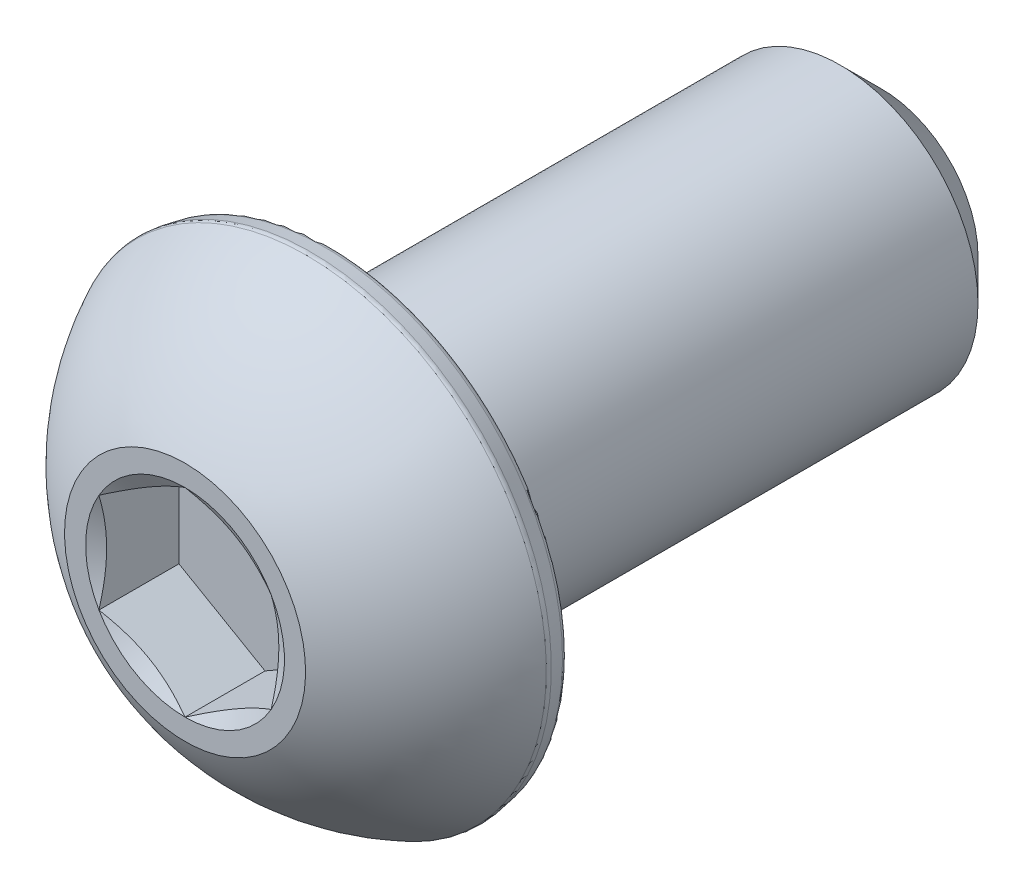
SolidWorks part; units mm, degrees
material "Plain Carbon Steel"
ref_plane "Front Plane" through (0, 0, 0) normal (0, 0, 1) x (1, 0, 0)
ref_plane "Top Plane" through (0, 0, 0) normal (0, 1, 0) x (1, 0, 0)
ref_plane "Right Plane" through (0, 0, 0) normal (1, 0, 0) x (0, 0, -1)
sketch "Sketch1" plane through (0, 0, 0) normal (1, 0, 0) x (0, 0, -1)
  line L0 (-8.0264, 0) -> (8.0264, 0) construction
  line L1 (-8.0264, 0) -> (-8.0264, 5.5499)
  line L2 (-8.0264, 5.5499) -> (-4.6736, 5.5499)
  line L3 (-4.6736, 5.5499) -> (-4.6736, 3.175)
  line L4 (-4.6736, 3.175) -> (8.0264, 3.175)
  line L5 (8.0264, 3.175) -> (8.0264, 0)
  point P2 (0, 0)
  point P4 (6.7564, 0)
  point P9 (6.1214, 3.175)
  point P10 (6.1214, -3.175)
  point P11 (8.0264, -3.175)
  point P15 (-6.1824, 0)
  dimension "Head Height" = 3.3528
  dimension "Head Diameter" = 11.0998
  dimension "Length" = 12.7
  dimension "Screw Size Decimal Equivalent" = 6.35
  dimension "Thread Pitch" = 1.27
  dimension "D1" = 1.905
  dimension "D2" = 1.844
sketch "Sketch2" plane through (0, 0, 0) normal (0, 0, 1) x (1, 0, 0)
  line L0 (0, 3.175) -> (0, 0) construction
  line L1 (0, 2.2914) -> (-1.9844, 1.1457)
  line L2 (-1.9844, 1.1457) -> (-1.9844, -1.1457)
  line L3 (-1.9844, -1.1457) -> (0, -2.2914)
  line L4 (0, -2.2914) -> (1.9844, -1.1457)
  line L5 (1.9844, -1.1457) -> (1.9844, 1.1457)
  line L6 (1.9844, 1.1457) -> (0, 2.2914)
  circle A0 centre (0, 0) radius 1.9844 construction
  circle A1 centre (0, 0) radius 2.7781
  point P10 (0, 2.7781)
  dimension "D1" = 5.5563
  dimension "Drive Size" = 3.9688
sketch "Sketch3" plane through (0, 0, 0) normal (1, 0, 0) x (0, 0, -1)
  line L0 (-8.0264, 0) -> (-8.0264, 2.7781)
  line L1 (-8.0264, 0) -> (-8.0264, 5.5499) construction
  line L2 (-8.0264, 5.5499) -> (-4.6736, 5.5499) construction
  line L3 (-5.1765, 5.5499) -> (-4.6736, 5.4612)
  line L4 (-4.6736, 5.5499) -> (-4.6736, 3.175) construction
  line L5 (-4.6736, 5.4612) -> (-4.6736, 3.175)
  line L6 (-8.0264, 0) -> (8.0264, 0) construction
  line L7 (-8.0264, 0) -> (8.0264, 0)
  line L8 (8.0264, 0) -> (8.0264, 2.2225)
  line L9 (8.0264, 3.175) -> (8.0264, 0) construction
  line L10 (8.0264, 2.2225) -> (7.0739, 3.175)
  line L11 (-4.6736, 3.175) -> (8.0264, 3.175) construction
  line L12 (7.0739, 3.175) -> (-4.6736, 3.175)
  arc A0 (-8.0264, 2.7781) -> (-5.1765, 5.5499) centre (-2.5516, 0) cw
  dimension "D1" = 0.5029
  dimension "D2" = 10
  dimension "D3" = 45
  dimension "D4" = 0.9525
revolve "Revolve1" add sketch "Sketch3" angle 360 about L7
sketch "Sketch4" plane through (0, 0, 8.0264) normal (0, 0, 1) x (1, 0, 0)
  line L0 (-1.9844, -1.1457) -> (0, -2.2914) construction
  line L1 (-1.9844, 1.1457) -> (-1.9844, -1.1457) construction
  line L2 (0, 2.2914) -> (-1.9844, 1.1457) construction
  line L3 (1.9844, 1.1457) -> (0, 2.2914) construction
  line L4 (1.9844, -1.1457) -> (1.9844, 1.1457) construction
  line L5 (0, -2.2914) -> (1.9844, -1.1457) construction
  line L6 (-1.9844, -1.1457) -> (0, -2.2914)
  line L7 (-1.9844, 1.1457) -> (-1.9844, -1.1457)
  line L8 (0, 2.2914) -> (-1.9844, 1.1457)
  line L9 (1.9844, 1.1457) -> (0, 2.2914)
  line L10 (1.9844, -1.1457) -> (1.9844, 1.1457)
  line L11 (0, -2.2914) -> (1.9844, -1.1457)
extrude "Cut-Extrude1" cut sketch "Sketch4" against normal up to vertex (1.844 mm away) up to point (0, 0, 6.1824)
sketch "Sketch5" plane through (0, 0, 8.0264) normal (0, 0, 1) x (1, 0, 0)
  circle A0 centre (0, 0) radius 2.2914
extrude "Cut-Extrude2" cut sketch "Sketch5" against normal up to vertex (1.844 mm away) draft 60 up to point (0, 0, 6.1824)
fillet "Fillet1" radius 0.1676 2 edges at (5.5499, 0, 5.1765) (5.4612, 0, 4.6736)
split "Split1" [suppressed] bodies to split 106
sketch "Sketch6" [suppressed] plane through (0, 0, -8.0264) normal (0, 0, -1) x (-1, 0, 0)
  circle A0 centre (0, 0) radius 3.175 construction
  circle A1 centre (0, 0) radius 3.175
curve "Helix/Spiral1" [suppressed] pitch 1.27 height 13.97 turns 11
sketch "Sketch7" [suppressed] plane through (0, 0, 0) normal (1, 0, 0) x (0, 0, -1)
  line L0 (7.947, 3.3125) -> (8.582, 2.2126) construction
  line L1 (8.582, 2.2126) -> (9.217, 3.3125) construction
  line L2 (9.217, 3.3125) -> (7.947, 3.3125) construction
  line L3 (7.9867, 3.2437) -> (9.1773, 3.2437)
  line L4 (9.1773, 3.2437) -> (8.6614, 2.3501)
  line L5 (8.6614, 2.3501) -> (8.5027, 2.3501)
  line L6 (8.5027, 2.3501) -> (7.9867, 3.2437)
  line L7 (8.582, 2.3501) -> (8.582, 2.2126) construction
  line L8 (8.0264, 3.175) -> (9.1377, 3.175) construction
  line L9 (8.582, 3.3125) -> (8.582, 3.175) construction
  point P12 (8.582, 3.2437)
  dimension "D1" = 1.27
  dimension "D2" = 0.1588
sweep "Cut-Sweep1" [suppressed] cut profiles "Sketch7" path "Helix/Spiral1"
sketch "Sketch8" [suppressed] plane through (0, 0, 4.6736) normal (0, 0, -1) x (-1, 0, 0)
  circle A0 centre (0, 0) radius 3.3125
extrude "Boss-Extrude1" [suppressed] add sketch "Sketch8" along normal up to vertex draft 45 up to point (0, 3.175, -6.1214)
equation "\"D1@Sketch1\"=\"Thread Pitch@Sketch1\"*1.5"
equation "\"D2@Sketch1\"=0.55*\"Head Height@Sketch1\""
equation "\"D1@Sketch2\"=\"Drive Size@Sketch2\"*1.4"
equation "\"D1@Sketch3\"=0.15*\"Head Height@Sketch1\""
equation "\"D4@Sketch3\"=0.75*\"Thread Pitch@Sketch1\""
equation "\"D1@Fillet1\"=.05*\"Head Height@Sketch1\""
equation "\"D4@Helix/Spiral1\"=\"Thread Pitch@Sketch1\""
equation "\"D3@Helix/Spiral1\"=\"Length@Sketch1\"+\"Thread Pitch@Sketch1\""
equation "\"D2@Sketch7\"=\"D1@Sketch7\"/8"
equation "\"D1@Sketch7\"=\"Thread Pitch@Sketch1\""
